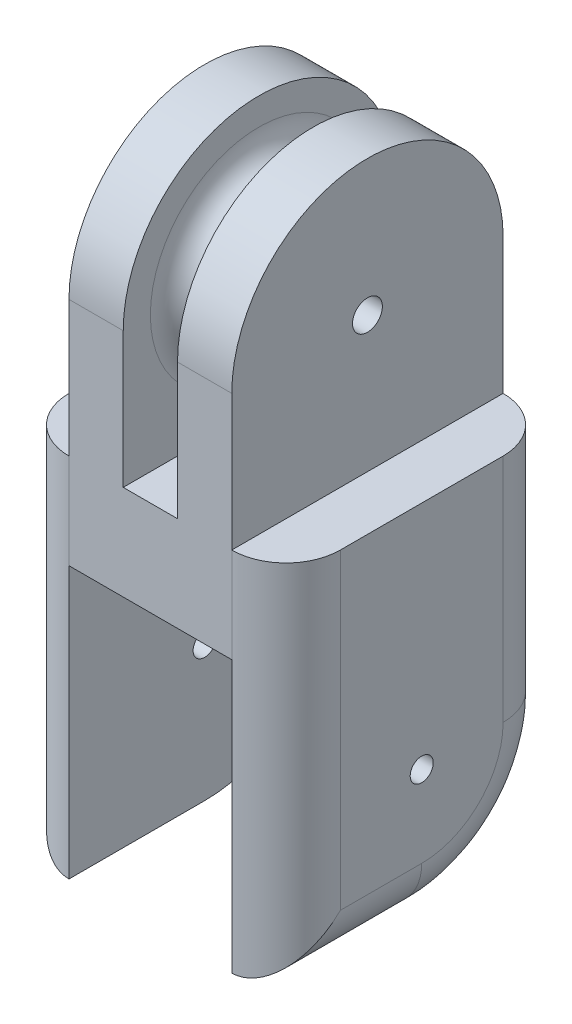
SolidWorks part; units mm, degrees
ref_plane "Front Plane" through (0, 0, 0) normal (0, 0, 1) x (1, 0, 0)
ref_plane "Top Plane" through (0, 0, 0) normal (0, 1, 0) x (1, 0, 0)
ref_plane "Right Plane" through (0, 0, 0) normal (1, 0, 0) x (0, 0, -1)
sketch "Sketch1" plane through (0, 0, 0) normal (0, 1, 0) x (1, 0, 0)
  line L0 (10, 10) -> (-10, -10) construction
  line L1 (-10, 10) -> (10, 10)
  line L2 (-10, 10) -> (-10, -10)
  line L3 (-10, -10) -> (10, -10)
  line L4 (10, 10) -> (10, -10)
  line L5 (-10, 10) -> (10, -10) construction
  point P5 (0, 0)
  dimension "D1" = 20
  dimension "D2" = 20
extrude "Boss-Extrude1" add sketch "Sketch1" along normal blind 7
sketch "Sketch4" plane through (0, 0, 0) normal (0, -1, 0) x (1, 0, 0)
  line L0 (10, -10) -> (-10, -10) construction
  line L1 (-10, 10) -> (-6, 10)
  line L2 (-10, 10) -> (-10, -10)
  line L3 (-10, -10) -> (-6, -10)
  line L4 (-6, 10) -> (-6, -10)
  line L5 (-10, 10) -> (10, 10) construction
  line L6 (10, -10) -> (6, -10)
  line L7 (10, -10) -> (10, 10)
  line L8 (10, 10) -> (6, 10)
  line L9 (6, -10) -> (6, 10)
  dimension "D1" = 4
  dimension "D2" = 4
extrude "Boss-Extrude2" add sketch "Sketch4" along normal blind 10
sketch "Sketch5" plane through (-10, 0, 0) normal (-1, 0, 0) x (0, 0, 1)
  line L0 (10, -10) -> (-10, -10) construction
  line L4 (0, -20) -> (10, -20)
  line L5 (10, -10) -> (10, -20)
  arc A0 (10, -10) -> (0, -20) centre (0, -10) ccw
extrude "Boss-Extrude3" add sketch "Sketch5" against normal blind 4
sketch "Sketch6" plane through (10, 0, 0) normal (1, 0, 0) x (0, 0, -1)
  line L0 (10, -10) -> (-10, -10) construction
  line L4 (0, -20) -> (-10, -20)
  line L5 (-10, -10) -> (-10, -20)
  arc A0 (0, -20) -> (-10, -10) centre (0, -10) ccw
extrude "Boss-Extrude4" add sketch "Sketch6" against normal blind 4
sketch "Sketch7" plane through (-10, 0, 0) normal (-1, 0, 0) x (0, 0, 1)
  circle A0 centre (0, -10) radius 0.85
  dimension "D1" = 1.7
extrude "Cut-Extrude1" cut sketch "Sketch7" against normal through all
fillet "Fillet1" radius 4 8 edges at (-10, -6.5, 10) (-10, -17.0711, -7.0711) (10, -6.5, 10) (10, -17.0711, -7.0711) (-10, -1.5, -10) (10, -1.5, -10) (10, -20, 5) (-10, -20, 5)
sketch "Sketch8" plane through (0, 7, 0) normal (0, 1, 0) x (1, 0, 0)
  line L0 (6, 10) -> (-6, 10) construction
  line L1 (6, -10) -> (2, -10)
  line L2 (6, -10) -> (6, 10)
  line L3 (6, 10) -> (2, 10)
  line L4 (2, -10) -> (2, 10)
  line L5 (-10, 6) -> (-10, -6) construction
  line L6 (-6, -10) -> (-2, -10)
  line L7 (-6, -10) -> (-6, 10)
  line L8 (-6, 10) -> (-2, 10)
  line L9 (-2, -10) -> (-2, 10)
  line L10 (10, -6) -> (10, 6) construction
  dimension "D1" = 4
  dimension "D2" = 4
  dimension "D3" = 4
  dimension "D4" = 4
extrude "Boss-Extrude5" add sketch "Sketch8" along normal blind 10
sketch "Sketch9" plane through (6, 0, 0) normal (1, 0, 0) x (0, 0, -1)
  line L0 (-10, 17) -> (10, 17) construction
  circle A0 centre (0, 17) radius 10
extrude "Boss-Extrude6" add sketch "Sketch9" against normal blind 4
sketch "Sketch10" plane through (-6, 0, 0) normal (-1, 0, 0) x (0, 0, 1)
  line L0 (-10, 17) -> (10, 17) construction
  circle A0 centre (0, 17) radius 10
extrude "Boss-Extrude7" add sketch "Sketch10" against normal blind 4
sketch "Sketch12" plane through (-6, 0, 0) normal (-1, 0, 0) x (0, 0, 1)
  circle A0 centre (0, 17) radius 1.1
  point P3 (0, 0)
  dimension "D1" = 2.2
extrude "Cut-Extrude2" cut sketch "Sketch12" against normal through all
sketch "Sketch13" plane through (-2, 0, 0) normal (1, 0, 0) x (0, 0, -1)
  circle A0 centre (0, 17) radius 6
  dimension "D1" = 12
sketch "Sketch14" plane through (-2, 0, 0) normal (1, 0, 0) x (0, 0, -1)
  circle A0 centre (0, 17) radius 1.1
  dimension "D1" = 2.2
extrude "Boss-Extrude8" add sketch "Sketch13" along normal blind 4
extrude "Cut-Extrude3" cut sketch "Sketch14" along normal blind 4
fillet "Fillet2" radius 2 2 edges at (2, 17, -6) (-2, 17, 6)
sketch "Sketch16" plane through (0, 0, 0) normal (0, -1, 0) x (1, 0, 0)
  line L0 (6, -10) -> (-6, -10) construction
  line L1 (-6, 0) -> (6, 0) construction
  line L2 (-6, -10) -> (-6, 10) construction
  line L3 (6, 10) -> (6, -10) construction
  circle A0 centre (0, -6) radius 0.5
  circle A1 centre (0, 6) radius 0.5
  dimension "D1" = 1
  dimension "D2" = 4
extrude "Cut-Extrude4" cut sketch "Sketch16" against normal up to next
